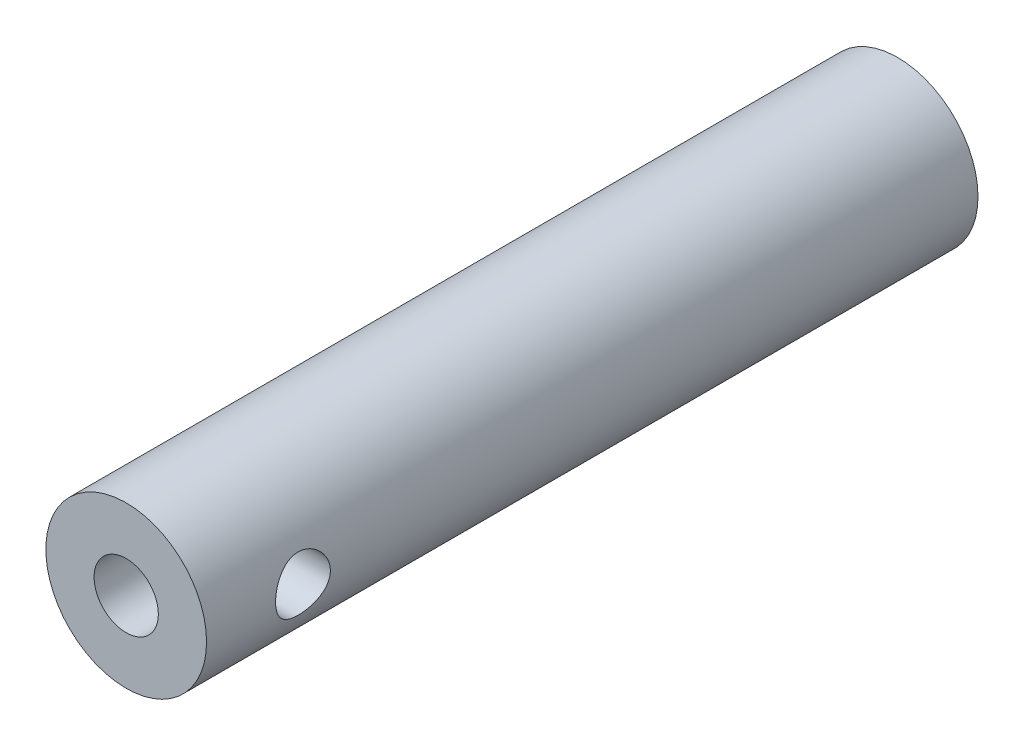
SolidWorks part; units mm, degrees
material "6061 Alloy"
ref_plane "Front Plane" through (0, 0, 0) normal (0, 0, 1) x (1, 0, 0)
ref_plane "Top Plane" through (0, 0, 0) normal (0, 1, 0) x (1, 0, 0)
ref_plane "Right Plane" through (0, 0, 0) normal (1, 0, 0) x (0, 0, -1)
sketch "Sketch1" plane through (0, 0, 0) normal (0, 0, 1) x (1, 0, 0)
  circle A0 centre (0, 0) radius 3.9688
  circle A1 centre (0, 0) radius 1.5875
  dimension "D1" = 7.9375
  dimension "D2" = 3.175
extrude "Body" add sketch "Sketch1" against normal blind 38.1 contours A1 | A0 A1 region at (-3.8565, 0, 0) region at (0, 0, 0)
extrude "POT Shaft Opening" cut sketch "Sketch1<3>" against normal blind 15.24 contours A1 region at (0, 0, 0)
sketch "Sketch1<3>" plane through (0, 0, 0) normal (0, 0, 1) x (1, 0, 0) same geometry as "Sketch1"
ref_plane "Plane1" through (3.9688, 0, 0) normal (1, 0, 0) x (0, 0, -1)
hole_wizard "#6-32 Tapped Hole1" positions "Sketch6" profile "Sketch5" tap size "#6-32" standard "Ansi Inch"
sketch "Sketch6" plane through (3.9688, 0, 0) normal (1, 0, 0) x (0, 0, -1)
  line L0 (0, 0) -> (4.7625, 0) construction
  point P0 (4.7625, 0)
  dimension "D1" = 4.7625
sketch "Sketch5" plane through (3.9688, 0, -4.7625) normal (0, 1, 0) x (0, 0, -1)
  line L0 (0, 0) -> (0, 4.6227)
  line L1 (0, 4.6227) -> (1.3525, 3.81)
  line L2 (1.3525, 3.81) -> (1.3525, 0)
  line L5 (1.3525, 0) -> (0, 0)
  line L10 (0, 4.6227) -> (-1.3525, 3.81) construction
  line L11 (0, -6.35) -> (0, 107.95) construction
  dimension "Tap Drill Dia." = 2.7051
  dimension "Tap Drill Depth" = 3.81
  dimension "Drill Angle" = 118
cosmetic thread "Hole Thread1" parameters "D1"=3.1376, "D2"=3.5052
